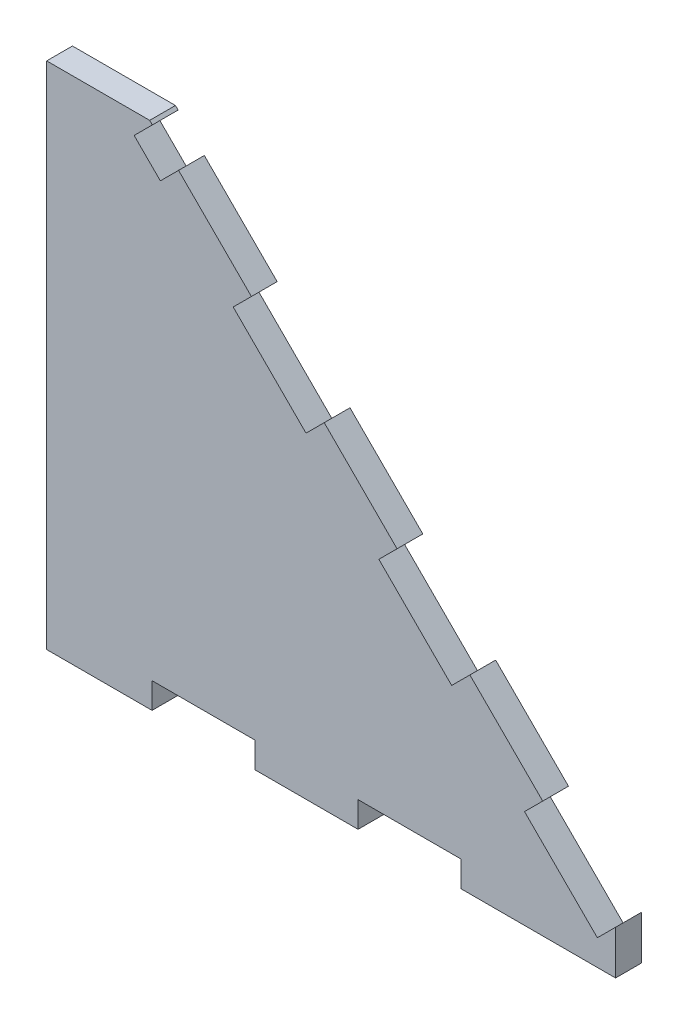
SolidWorks part; units mm, degrees
material "Acrylic (Medium-high impact)"
ref_plane "Front Plane" through (0, 0, 0) normal (0, 0, 1) x (1, 0, 0)
ref_plane "Top Plane" through (0, 0, 0) normal (0, 1, 0) x (1, 0, 0)
ref_plane "Right Plane" through (0, 0, 0) normal (1, 0, 0) x (0, 0, -1)
sketch "Sketch2" plane through (0, 0, 0) normal (0, 0, 1) x (1, 0, 0)
  line L0 (12.7, 62.8618) -> (70.1417, 5.4201)
  line L1 (0, 0) -> (127, 0)
  line L2 (0, 0) -> (0, 62.8618)
  line L3 (0, 62.8618) -> (127, 62.8618)
  line L4 (127, 0) -> (127, 62.8618)
  line L13 (70.1417, 5.4201) -> (70.1417, 0)
  line L14 (61.1615, 14.4003) -> (70.1417, 5.4201)
  line L15 (61.1615, 14.4003) -> (58.9164, 12.1553)
  line L16 (70.1417, 5.4201) -> (67.8967, 3.175)
  line L17 (58.9164, 12.1553) -> (67.8967, 3.175)
  line L18 (70.1417, 5.4201) -> (88.975, -13.4132) construction
  line L19 (43.201, 32.3608) -> (52.1812, 23.3806)
  line L20 (43.201, 32.3608) -> (40.9559, 30.1158)
  line L21 (40.9559, 30.1158) -> (49.9362, 21.1355)
  line L22 (52.1812, 23.3806) -> (49.9362, 21.1355)
  line L23 (25.2404, 50.3213) -> (34.2207, 41.3411)
  line L24 (25.2404, 50.3213) -> (22.9954, 48.0763)
  line L25 (22.9954, 48.0763) -> (31.9756, 39.096)
  line L26 (34.2207, 41.3411) -> (31.9756, 39.096)
  line L27 (13.0273, 62.5345) -> (16.2602, 59.3016)
  line L28 (13.0273, 62.5345) -> (10.7822, 60.2894)
  line L29 (16.2602, 59.3016) -> (14.0151, 57.0565)
  line L30 (10.7822, 60.2894) -> (14.0151, 57.0565)
  point P7 (0, 0)
  dimension "D1" = 62.8618
  dimension "D2" = 3.175
  dimension "D3" = 12.7
  dimension "D4" = 45
  dimension "D5" = 3.175
  dimension "D6" = 12.7
  dimension "D8" = 12.7
  dimension "D9" = 12.7
  dimension "D10" = 4.572
  dimension "D11" = 127
  dimension "D7" = 3
extrude "Boss-Extrude1" add sketch "Sketch2" along normal blind 3.175 contours L30 L28 L0 L3 L2 L1 L13 L16 L17 L15 L22 L21 L20 L26 L25 L24 L29 region at (24.6483, 23.7667, 0)
sketch "Sketch3" plane through (0, 0, 3.175) normal (0, 0, 1) x (1, 0, 0)
  line L0 (0, 0) -> (70.1417, 0) construction
  line L1 (38.3917, 0) -> (51.0917, 0)
  line L2 (38.3917, 0) -> (38.3917, 3.175)
  line L3 (38.3917, 3.175) -> (51.0917, 3.175)
  line L4 (51.0917, 0) -> (51.0917, 3.175)
  line L5 (70.1417, 5.4201) -> (70.1417, 0) construction
  line L7 (12.9917, 0) -> (25.6917, 0)
  line L8 (12.9917, 0) -> (12.9917, 3.175)
  line L9 (12.9917, 3.175) -> (25.6917, 3.175)
  line L10 (25.6917, 0) -> (25.6917, 3.175)
  dimension "D1" = 3.175
  dimension "D2" = 19.05
  dimension "D3" = 12.7
  dimension "D4" = 12.7
  dimension "D5" = 12.7
extrude "Cut-Extrude1" cut sketch "Sketch3" against normal through all and the other way through all
